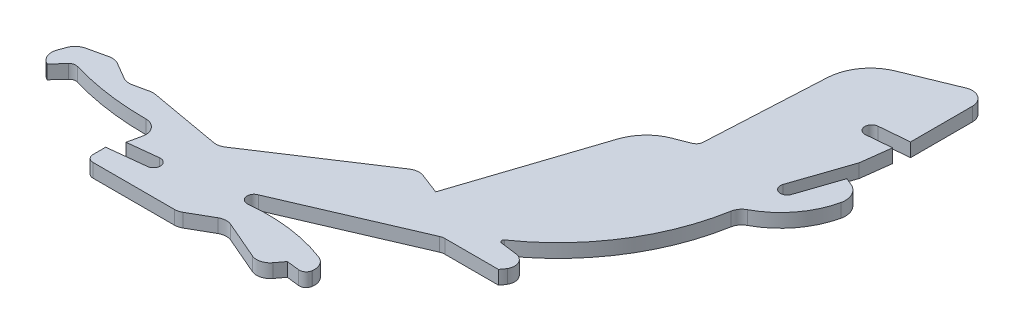
SolidWorks part; units mm, degrees
ref_plane "Front Plane" through (0, 0, 0) normal (0, 0, 1) x (1, 0, 0)
ref_plane "Top Plane" through (0, 0, 0) normal (0, 1, 0) x (1, 0, 0)
ref_plane "Right Plane" through (0, 0, 0) normal (1, 0, 0) x (0, 0, -1)
sketch "Sketch2" plane through (0, 0, 0) normal (0, 1, 0) x (1, 0, 0)
  line L0 (104.8617, 51.61) -> (96.2857, 51.61)
  line L1 (96.2857, 48.61) -> (104.8617, 48.61)
  line L2 (104.8617, 48.61) -> (104.8617, 42.36)
  line L3 (107.0706, 39.34) -> (104.0266, 29.4584)
  line L4 (101.1595, 30.3416) -> (104.8617, 42.36)
  line L5 (105.5312, 18.3607) -> (111.09, 27.1258)
  line L6 (104.8617, 51.61) -> (107.0706, 55.46)
  line L7 (89.7728, 69.8362) -> (57.4, 86.17)
  line L8 (41.6529, 73.6621) -> (36.03, 31.3784)
  line L9 (36.03, 31.3784) -> (29.1482, 28.9869)
  line L10 (29.1482, 28.9869) -> (21.9915, 21.0198)
  line L11 (21.9915, 21.0198) -> (8.1869, 15.1615)
  line L12 (0, 0) -> (0, 4.28)
  line L13 (0, 4.28) -> (8.2554, 5.2)
  line L14 (7.9231, 8.1815) -> (-3.1214, 6.9507)
  line L15 (-3.1214, 6.9507) -> (-7.4992, 8.4826)
  line L16 (-7.4992, 8.4826) -> (-11.8276, 7.2216)
  line L17 (-11.8276, 7.2216) -> (-19.2552, 11.2976)
  line L18 (-19.2552, 11.2976) -> (-23.2053, 10.8574)
  line L19 (-23.2053, 10.8574) -> (-22.2697, 7.6463)
  line L20 (-22.2697, 7.6463) -> (-24.8125, 7.2216)
  line L21 (0, 0) -> (20.16, 0)
  line L22 (20.16, 0) -> (27.0155, 3.9247)
  line L23 (27.0155, 3.9247) -> (38.9, -1.2)
  line L24 (38.9, -1.2) -> (41.66, 2.4827)
  line L25 (41.66, 2.4827) -> (45.9, 1.9915)
  line L26 (45.9, 1.9915) -> (46.4657, 5.8541)
  line L27 (25.83, 11.99) -> (49.95, 19.39)
  line L28 (49.95, 19.39) -> (57.13, 16.32)
  line L29 (57.13, 16.32) -> (61.9358, 23.0276)
  line L30 (61.9358, 23.0276) -> (67.6517, 44.29)
  arc A0 (96.2857, 51.61) -> (96.2857, 48.61) centre (96.2857, 50.11) ccw
  arc A1 (107.0706, 39.34) -> (111.09, 27.1258) centre (97.2099, 29.3266) cw
  arc A2 (104.0266, 29.4584) -> (101.1595, 30.3416) centre (102.5931, 29.9) cw
  arc A3 (107.0706, 55.46) -> (93.2591, 66.4439) centre (93.6334, 52.7391) ccw
  arc A4 (93.2591, 66.4439) -> (89.7728, 69.8362) centre (93.1665, 69.8362) cw
  arc A5 (57.4, 86.17) -> (41.6529, 73.6621) centre (56.0104, 71.7528) ccw
  arc A6 (8.1869, 15.1615) -> (-17.7049, 14.5311) centre (-5.6083, 49.7338) cw
  arc A7 (8.2554, 5.2) -> (7.9231, 8.1815) centre (8.0892, 6.6908) ccw
  arc A8 (-24.8125, 7.2216) -> (-27.5, 15.12) centre (-19.6156, 13.3963) cw
  arc A9 (-27.5, 15.12) -> (-17.7049, 14.5311) centre (-22.91, 9.71) cw
  arc A10 (46.4657, 5.8541) -> (26.4315, 9.0647) centre (30.5748, -29.1928) ccw
  arc A11 (26.4315, 9.0647) -> (25.83, 11.99) centre (26.27, 10.556) cw
  arc A12 (67.6517, 44.29) -> (105.5312, 18.3607) centre (122.4523, 83.7134) ccw
  point P4 (0, 0)
  point P9 (102.1515, 28.4665)
  point P12 (94.7857, 50.11)
  point P13 (-27.5, 15.12)
  point P72 (9.58, 6.8569)
  dimension "D6" = 1.5
  dimension "D11" = 1.5
  dimension "D32" = 14.0535
  dimension "D33" = 13.7098
  dimension "D34" = 3.3937
  dimension "D35" = 14.484
  dimension "D36" = 37.223
  dimension "D37" = 8.0706
  dimension "D38" = 7.0948
  dimension "D39" = 38.4812
  dimension "D40" = 67.5078
  dimension "D75" = 1.5
  dimension "D1" = 51.61
  dimension "D2" = 111.09
  dimension "D3" = 10.076
  dimension "D4" = 27.5
  dimension "D5" = 15.12
  dimension "D7" = 29.9
  dimension "D8" = 39.34
  dimension "D9" = 6.25
  dimension "D10" = 102.5931
  dimension "D12" = 4.28
  dimension "D13" = 20.16
  dimension "D14" = 5.14
  dimension "D15" = 1.2
  dimension "D16" = 45.9
  dimension "D17" = 38.9
  dimension "D18" = 86.17
  dimension "D19" = 9.58
  dimension "D20" = 5.2
  dimension "D21" = 11.99
  dimension "D22" = 16.32
  dimension "D23" = 57.13
  dimension "D24" = 49.95
  dimension "D25" = 26.27
  dimension "19.39" = 19.39
  dimension "D26" = 84.9
  dimension "D27" = 63.53
  dimension "D28" = 37.21
  dimension "D29" = 44.29
  dimension "D30" = 3.85
  dimension "D31" = 20
  dimension "D41" = 8.1869
  dimension "D42" = 21.9915
  dimension "D43" = 26.4315
  dimension "D44" = 27.0155
  dimension "D45" = 29.1482
  dimension "D46" = 41.6529
  dimension "D47" = 41.66
  dimension "D48" = 46.4657
  dimension "D49" = 56.0104
  dimension "D50" = 61.9358
  dimension "D51" = 67.6517
  dimension "D52" = 89.7728
  dimension "D53" = 97.2099
  dimension "D54" = 105.5312
  dimension "D55" = 122.4523
  dimension "D56" = 3.1214
  dimension "D57" = 5.6083
  dimension "D58" = 7.4992
  dimension "D59" = 11.8276
  dimension "D60" = 17.7049
  dimension "D61" = 19.2552
  dimension "D62" = 19.6156
  dimension "D63" = 22.2697
  dimension "D64" = 22.91
  dimension "D65" = 23.2053
  dimension "D66" = 24.8125
  dimension "D67" = 1.9915
  dimension "D68" = 2.4827
  dimension "D69" = 7.6463
  dimension "D70" = 8.4826
  dimension "D71" = 11.2976
  dimension "D72" = 21.0198
  dimension "D73" = 23.0276
  dimension "D74" = 28.9869
sketch "Sketch3" plane through (0, 0, 0) normal (0, 1, 0) x (1, 0, 0)
  line L0 (7.9231, 8.1815) -> (1.2884, 7.4422)
  line L1 (45.9, 1.9915) -> (46.4657, 5.8541) construction
  line L2 (41.66, 2.4827) -> (45.9, 1.9915) construction
  line L3 (38.9, -1.2) -> (41.66, 2.4827) construction
  line L4 (27.0155, 3.9247) -> (38.9, -1.2) construction
  line L5 (20.16, 0) -> (27.0155, 3.9247) construction
  line L6 (0, 4.28) -> (8.2554, 5.2) construction
  line L7 (0, 0) -> (0, 4.28) construction
  line L8 (0, 0) -> (20.16, 0) construction
  line L9 (1.2884, 7.4422) -> (2.7682, 14.19)
  line L10 (45.9, 1.9915) -> (46.4657, 5.8541)
  line L11 (41.66, 2.4827) -> (45.9, 1.9915)
  line L12 (38.9, -1.2) -> (41.66, 2.4827)
  line L13 (27.0155, 3.9247) -> (38.9, -1.2)
  line L14 (20.16, 0) -> (27.0155, 3.9247)
  line L15 (0, 4.28) -> (8.2554, 5.2)
  line L16 (0, 0) -> (0, 4.28)
  line L17 (0, 0) -> (20.16, 0)
  line L18 (-19.3597, 16.8) -> (-22.2168, 13.6663)
  line L19 (-22.2168, 13.6663) -> (-24.8203, 14.623)
  line L20 (-24.8203, 14.623) -> (-22.6465, 20.5386)
  line L21 (-22.6465, 20.5386) -> (-15.7038, 22.1118)
  line L22 (-15.7038, 22.1118) -> (-10.0733, 18.8185)
  line L23 (-10.0733, 18.8185) -> (-5.1865, 19.8808)
  line L24 (-5.1865, 19.8808) -> (12.13, 16.8)
  line L25 (12.13, 16.8) -> (38.76, 34.29)
  line L26 (87.31, 93.5914) -> (80.7227, 93.015)
  line L27 (80.9841, 90.0265) -> (86.4632, 90.5058)
  line L28 (87.31, 93.5914) -> (87.31, 111.63)
  line L29 (87.31, 111.63) -> (66.29, 103.0079)
  line L32 (66.29, 103.0079) -> (64.5523, 69.7569)
  line L33 (64.5523, 69.7569) -> (56.0586, 66.407)
  line L34 (56.0586, 66.407) -> (44.7, 32)
  line L35 (44.7, 32) -> (38.76, 34.29)
  line L36 (25.83, 11.99) -> (54.05, 24.15)
  line L37 (54.05, 24.15) -> (66.29, 24.15)
  line L38 (68.0387, 28.663) -> (60.2978, 29.686)
  line L39 (87.31, 79.61) -> (91.6185, 77.8876)
  line L40 (87.31, 79.61) -> (84.2303, 70.5437)
  line L41 (81.3897, 71.5086) -> (85.6329, 84)
  line L42 (85.6329, 84) -> (86.4632, 90.5058)
  arc A0 (25.83, 11.99) -> (26.4315, 9.0647) centre (26.27, 10.556) ccw construction
  arc A1 (46.4657, 5.8541) -> (26.4315, 9.0647) centre (30.5748, -29.1928) ccw construction
  arc A3 (25.83, 11.99) -> (26.4315, 9.0647) centre (26.27, 10.556) ccw
  arc A4 (46.4657, 5.8541) -> (26.4315, 9.0647) centre (30.5748, -29.1928) ccw
  arc A5 (8.2554, 5.2) -> (7.9231, 8.1815) centre (8.0892, 6.6908) ccw
  arc A6 (2.7682, 14.19) -> (-19.3597, 16.8) centre (-1.1426, 76.1401) cw
  arc A7 (80.7227, 93.015) -> (80.9841, 90.0265) centre (80.8534, 91.5207) ccw
  arc A8 (66.29, 24.15) -> (68.0387, 28.663) centre (61.3409, 28.663) ccw
  arc A9 (60.2978, 29.686) -> (80.9841, 62.2084) centre (34.8127, 68.7363) ccw
  arc A10 (91.6185, 77.8876) -> (80.9841, 62.2084) centre (74.0824, 78.3355) cw
  arc A11 (84.2303, 70.5437) -> (81.3897, 71.5086) centre (82.81, 71.0261) cw
  point P20 (87.31, 111.63)
  point P28 (87.31, 79.61)
  point P36 (79.0524, 100.0453)
  point P37 (-20.0892, 16.8)
  point P40 (79.3591, 91.39)
  point P55 (0, 2.14)
  point P57 (85.8315, 84.5846)
  point P58 (0, 0)
  point P59 (63.5891, 99.3953)
  point P60 (54.05, 69.7569)
  point P61 (0, 0)
  point P62 (56.0586, 66.407)
  point P63 (66.29, 103.0079)
  point P64 (85.6329, 111.63)
  point P65 (82.81, 110.1798)
  point P66 (0, 0)
  point P67 (0, 0)
  point P68 (2.7682, 11.99)
  point P69 (-19.3597, 16.8)
  point P70 (0, 0)
  point P77 (9.58, 6.8569)
  point P90 (82.3275, 69.6058)
  dimension "D5" = 1.5
  dimension "D22" = 62.0734
  dimension "D23" = 6.6978
  dimension "D24" = 46.6306
  dimension "D25" = 17.5418
  dimension "D1" = 111.63
  dimension "D2" = 87.31
  dimension "D3" = 79.61
  dimension "D4" = 17.97
  dimension "D6" = 8.25
  dimension "95" = 95
  dimension "D7" = 54.05
  dimension "D8" = 44.7
  dimension "D9" = 32
  dimension "D10" = 24.15
  dimension "D11" = 16.8
  dimension "D12" = 2.55
  dimension "D13" = 38.76
  dimension "D14" = 2.29
  dimension "D15" = 66.29
  dimension "D16" = 4.64
  dimension "D17" = 23.46
  dimension "D18" = 82.81
  dimension "D19" = 84
  dimension "D20" = 5.5
  dimension "D21" = 14.19
  dimension "D26" = 1.2884
  dimension "D27" = 2.7682
  dimension "D28" = 34.8127
  dimension "D29" = 56.0586
  dimension "D30" = 60.2978
  dimension "D31" = 61.3409
  dimension "D32" = 64.5523
  dimension "D33" = 68.0387
  dimension "D34" = 74.0824
  dimension "D35" = 1.1426
  dimension "D36" = 13.6663
  dimension "D37" = 14.623
  dimension "D38" = 91.6185
  dimension "D39" = 18.8185
  dimension "D40" = 5.1865
  dimension "D41" = 10.0733
  dimension "D42" = 15.7038
  dimension "D43" = 19.8808
  dimension "D44" = 22.2168
  dimension "D45" = 22.6465
  dimension "D46" = 24.8203
  dimension "D48" = 22.1118
  dimension "D49" = 66.407
  dimension "D51" = 69.7569
  dimension "D53" = 103.0079
extrude "Boss-Extrude1" add sketch "Sketch3" along normal blind 3
fillet "Fillet1" radius 3 13 edges at (-24.8203, 1.5, -14.623) (80.9841, 1.5, -62.2084) (20.16, 1.5, 0) (46.4657, 1.5, -5.8541) (38.9, 1.5, 1.2) (27.0155, 1.5, -3.9247) (38.76, 1.5, -34.29) (12.13, 1.5, -16.8) (-5.1865, 1.5, -19.8808) (-10.0733, 1.5, -18.8185) (-15.7038, 1.5, -22.1118) (-22.6465, 1.5, -20.5386) (2.7682, 1.5, -14.19)
fillet "Fillet2" radius 1.5 4 edges at (64.5523, 1.5, -69.7569) (45.9, 1.5, -1.9915) (0, 1.5, 0) (-19.3597, 1.5, -16.8)
fillet "Fillet3" radius 10 2 edges at (56.0586, 1.5, -66.407) (66.29, 1.5, -103.0079)
fillet "Fillet4" radius 3 1 edges at (87.31, 1.5, -111.63)
fillet "Fillet5" radius 4 1 edges at (91.6185, 1.5, -77.8876)
fillet "Fillet6" radius 2.5 2 edges at (68.0387, 1.5, -28.663) (54.05, 1.5, -24.15)
fillet "Fillet7" radius 0.5 1 edges at (60.2978, 1.5, -29.686)
